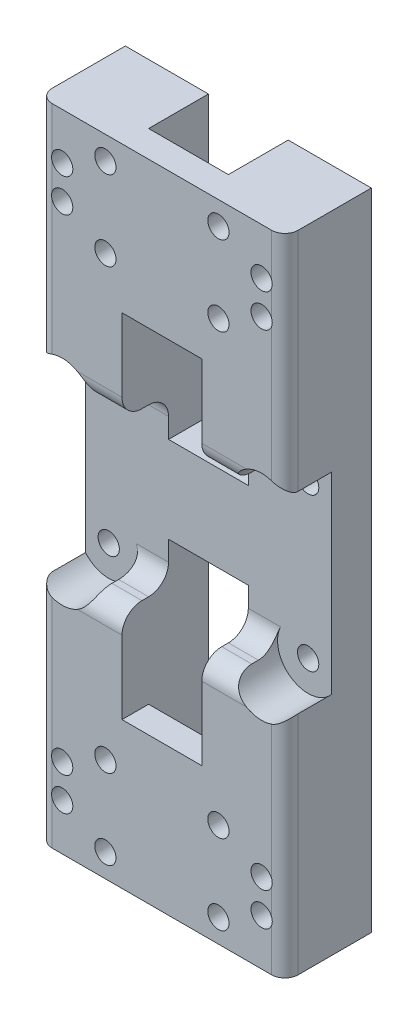
SolidWorks part; units mm, degrees
ref_plane "Front Plane" through (0, 0, 0) normal (0, 0, 1) x (1, 0, 0)
ref_plane "Top Plane" through (0, 0, 0) normal (0, 1, 0) x (1, 0, 0)
ref_plane "Right Plane" through (0, 0, 0) normal (1, 0, 0) x (0, 0, -1)
sketch "Sketch1" plane through (0, 0, 0) normal (0, 0, 1) x (1, 0, 0)
  line L1 (6, 11) -> (-6, 11)
  line L2 (6, 11) -> (6, -11)
  line L3 (6, -11) -> (-6, -11)
  line L4 (-6, 11) -> (-6, -11)
  line L5 (6, 11) -> (-6, -11) construction
  line L6 (6, -11) -> (-6, 11) construction
  line L7 (11, 11) -> (-11, 11)
  line L8 (11, 11) -> (11, -11)
  line L9 (11, -11) -> (-11, -11)
  line L10 (-11, 11) -> (-11, -11)
  line L11 (11, 11) -> (-11, -11) construction
  line L12 (11, -11) -> (-11, 11) construction
  point P0 (0, 0)
  point P6 (0, 0)
  dimension "D1" = 12
  dimension "D2" = 22
  dimension "D3" = 0
  dimension "D4" = 5
extrude "Boss-Extrude1" add sketch "Sketch1" along normal blind 9 contours L9 L8 L7 L2 | L7 L10 L9 L4 region at (8.5, 0, 0) region at (-8.5, 0, 0)
sketch "Sketch2" plane through (0, 0, 9) normal (0, 0, 1) x (1, 0, 0)
  line L0 (11, -11) -> (6, -11) construction
  line L1 (-11, 11) -> (11, 11)
  line L2 (-11, 11) -> (-11, -11)
  line L3 (-11, -11) -> (11, -11)
  line L4 (11, 11) -> (11, -11)
  line L5 (11, 11) -> (11, -11) construction
extrude "Boss-Extrude2" add sketch "Sketch2" along normal blind 4
sketch "Sketch3" plane through (0, 0, 0) normal (0, 0, -1) x (-1, 0, 0)
  line L0 (-6, 11) -> (-6, -11) construction
  line L1 (6, 11) -> (6, -11) construction
  line L2 (-6, 11) -> (-6, -11) construction
  line L3 (6, -11) -> (11, -11) construction
  line L4 (-11, -11) -> (-6, -11) construction
  circle A0 centre (8.5, 4.5) radius 1.6
  circle A1 centre (8.5, -7.5) radius 1.6
  circle A2 centre (-8.5, 4.5) radius 1.6
  circle A3 centre (-8.5, -7.5) radius 1.6
  dimension "D1" = 3.2
  dimension "D2" = 3.2
  dimension "D3" = 3.2
  dimension "D4" = 3.2
  dimension "D5" = 3.2
  dimension "D6" = 2.5
  dimension "D7" = 2.5
  dimension "D8" = 2.5
  dimension "D9" = 2.5
  dimension "D10" = 12
  dimension "D11" = 12
  dimension "D12" = 3.5
  dimension "D13" = 3.5
extrude "Cut-Extrude1" cut sketch "Sketch3" against normal through all
sketch "Sketch4" plane through (0, 0, 13) normal (0, 0, 1) x (1, 0, 0)
  line L1 (11, 11) -> (12.5, 11)
  line L2 (11, 11) -> (11, -11)
  line L3 (11, -11) -> (12.5, -11)
  line L4 (12.5, 11) -> (12.5, -11)
  line L5 (-11, 11) -> (-12.5, 11)
  line L6 (-11, 11) -> (-11, -11)
  line L7 (-11, -11) -> (-12.5, -11)
  line L8 (-12.5, 11) -> (-12.5, -11)
  circle A0 centre (8.5, 4.5) radius 1.6 construction
  circle A1 centre (-8.5, 4.5) radius 1.6 construction
  dimension "D1" = 4
  dimension "D2" = 4
extrude "Boss-Extrude3" add sketch "Sketch4" against normal up to surface (13 mm away) up to face at (6.9, 4.5, 0)
sketch "Sketch5" plane through (0, 0, 13) normal (0, 0, 1) x (1, 0, 0)
  line L1 (-12.5, -11) -> (-18.5, -11)
  line L2 (-12.5, -11) -> (-12.5, 11)
  line L3 (-12.5, 11) -> (-18.5, 11)
  line L4 (-18.5, -11) -> (-18.5, 11)
  line L5 (12.5, 11) -> (18.5, 11)
  line L6 (12.5, 11) -> (12.5, -11)
  line L7 (12.5, -11) -> (18.5, -11)
  line L8 (18.5, 11) -> (18.5, -11)
  dimension "D1" = 6
  dimension "D2" = 6
extrude "Boss-Extrude4" add sketch "Sketch5" against normal up to surface (13 mm away) up to face at (-10.1, -7.5, 0)
sketch "Sketch6" plane through (0, 0, 0) normal (0, 0, -1) x (-1, 0, 0)
  line L1 (18.5, -11) -> (18.5, 11) construction
  line L2 (6, -11) -> (18.5, -11) construction
  line L3 (0, 19.1577) -> (0, -22.4017) construction
  circle A0 centre (15, 1) radius 1.6
  circle A1 centre (15, -4) radius 1.6
  circle A2 centre (-15, -4) radius 1.6
  circle A3 centre (-15, 1) radius 1.6
  dimension "D1" = 3.2
  dimension "D2" = 7
  dimension "D3" = 3.5
  dimension "D4" = 3.5
  dimension "D5" = 5
  dimension "D6" = 3.2
extrude "Cut-Extrude2" cut sketch "Sketch6" against normal blind 21
sketch "Sketch7" plane through (0, 0, 13) normal (0, 0, 1) x (1, 0, 0)
  line L1 (18.5, 11) -> (6, 11)
  line L2 (18.5, 11) -> (18.5, 37.5)
  line L3 (18.5, 37.5) -> (6, 37.5)
  line L4 (6, 11) -> (6, 37.5)
  line L5 (-18.5, 11) -> (-6, 11)
  line L6 (-18.5, 11) -> (-18.5, 37.5)
  line L7 (-18.5, 37.5) -> (-6, 37.5)
  line L8 (-6, 11) -> (-6, 37.5)
  dimension "D1" = 12.5
  dimension "D2" = 12.5
  dimension "D3" = 26.5
  dimension "D4" = 26.5
extrude "Boss-Extrude5" add sketch "Sketch7" against normal up to surface (13 mm away) up to face at (16.6, 1, 0)
mirror "Mirror1" about plane through (-18.5, 37.5, -29.3002) normal (0, 1, 0) of bodies 112
sketch "Sketch8" plane through (0, 0, 13) normal (0, 0, 1) x (1, 0, 0)
  line L0 (-18.5, 86) -> (18.5, 86) construction
  line L1 (-22.3226, 56) -> (24.6395, 56)
  line L2 (-22.3226, 56) -> (-22.3226, 19)
  line L3 (-22.3226, 19) -> (24.6395, 19)
  line L4 (24.6395, 56) -> (24.6395, 19)
  line L5 (-18.5, -11) -> (18.5, -11) construction
  dimension "D1" = 30
  dimension "D2" = 30
extrude "Cut-Extrude3" cut sketch "Sketch8" against normal blind 7 contours L2 L1 L4 L3
sketch "Sketch10" plane through (0, 0, 6) normal (0, 0, 1) x (1, 0, 0)
  line L0 (-18.5, -11) -> (18.5, -11) construction
  line L1 (-18.5, 56) -> (-18.5, 19) construction
  line L2 (18.5, 19) -> (18.5, 56) construction
  line L3 (-18.5, 37.5) -> (40.3444, 37.5) construction
  circle A0 centre (-15, 26) radius 1.6
  circle A1 centre (15, 26) radius 1.6
  circle A3 centre (15, 49) radius 1.6
  circle A4 centre (-15, 49) radius 1.6
  dimension "D1" = 3.2
  dimension "D2" = 3.2
  dimension "D3" = 37
  dimension "D4" = 37
  dimension "D5" = 3.5
  dimension "D6" = 3.5
extrude "Cut-Extrude4" cut sketch "Sketch10" against normal blind 6
sketch "Sketch11" plane through (0, 0, 13) normal (0, 0, 1) x (1, 0, 0)
  line L0 (-18.5, 56) -> (-18.5, 19) construction
  line L1 (-6, 11) -> (-18.5, 11)
  line L2 (-6, 11) -> (-6, 25)
  line L3 (-6, 25) -> (-18.5, 25)
  line L4 (-18.5, 11) -> (-18.5, 25)
  line L5 (18.5, 19) -> (18.5, 56) construction
  line L6 (6, 11) -> (18.5, 11)
  line L7 (6, 11) -> (6, 25)
  line L8 (6, 25) -> (18.5, 25)
  line L9 (18.5, 11) -> (18.5, 25)
  line L10 (-18.5, 37.5) -> (18.5, 37.5) construction
  line L11 (6, 50) -> (18.5, 50)
  line L12 (18.5, 64) -> (18.5, 50)
  line L13 (6, 64) -> (18.5, 64)
  line L14 (6, 64) -> (6, 50)
  line L15 (-6, 50) -> (-18.5, 50)
  line L16 (-18.5, 64) -> (-18.5, 50)
  line L17 (-6, 64) -> (-18.5, 64)
  line L18 (-6, 64) -> (-6, 50)
  dimension "D1" = 14
  dimension "D2" = 14
extrude "Boss-Extrude6" add sketch "Sketch11" along direction (0, 0, -1) on the side against the normal up to surface (7 mm away) up to face at (13.4, 49, 6)
fillet "Fillet3" radius 3 2 edges at (15, 25, 6) (-15, 25, 6)
sketch "Sketch13" plane through (0, 0, 19) normal (0, 0, 1) x (1, 0, 0)
  line L0 (-18.5, 37.5) -> (28.7617, 37.5) construction
  line L1 (-18.5, 50) -> (-18.5, 25) construction
  circle A0 centre (-15, 26) radius 4.6
  circle A1 centre (15, 26) radius 4.6
  circle A2 centre (-15, 26) radius 1.6 construction
  circle A3 centre (15, 26) radius 1.6 construction
  circle A4 centre (15, 49) radius 4.6
  circle A5 centre (-15, 49) radius 4.6
  dimension "D1" = 3
  dimension "D2" = 3
extrude "Cut-Extrude5" cut sketch "Sketch13" against normal up to surface (13 mm away) up to face at (13.625, 37.5, 6)
fillet "Fillet4" radius 3 8 edges at (-8.255, 25, 13) (8.255, 25, 13) (8.255, 50, 13) (-8.255, 50, 13) (-8.255, 25, 6) (8.255, 25, 6) (8.255, 50, 6) (-8.255, 50, 6)
sketch "Sketch14" plane through (0, 0, 6) normal (0, 0, 1) x (1, 0, 0)
  line L0 (6, 28) -> (6, 47) construction
  line L1 (6, 31) -> (-6, 31)
  line L2 (6, 31) -> (6, 44)
  line L3 (6, 44) -> (-6, 44)
  line L4 (-6, 31) -> (-6, 44)
  line L5 (-6, 28) -> (-6, 47) construction
  line L6 (10.8575, 47) -> (6, 47) construction
  line L7 (6, 28) -> (10.8575, 28) construction
  dimension "D1" = 3
  dimension "D2" = 3
extrude "Boss-Extrude8" add sketch "Sketch14" against normal blind 6
fillet "Fillet5" radius 2 4 edges at (-18.5, 68.9925, 13) (-18.5, 6.0075, 13) (18.5, 6.0075, 13) (18.5, 68.9925, 13)
